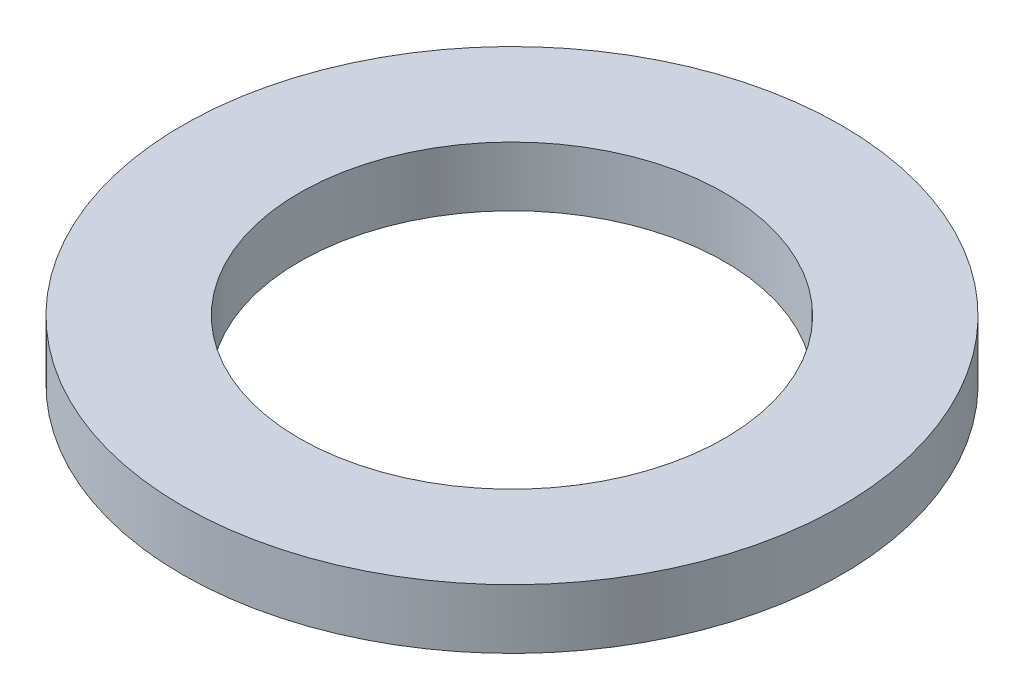
SolidWorks part; units mm, degrees
ref_plane "Front Plane" through (0, 0, 0) normal (0, 0, 1) x (1, 0, 0)
ref_plane "Top Plane" through (0, 0, 0) normal (0, 1, 0) x (1, 0, 0)
ref_plane "Right Plane" through (0, 0, 0) normal (1, 0, 0) x (0, 0, -1)
sketch "Sketch1" plane through (0, 0, 0) normal (0, 1, 0) x (1, 0, 0)
  circle A0 centre (0, 0) radius 77.5
  dimension "FLANGE_OD" = 155
extrude "Boss-Extrude1" add sketch "Sketch1" along normal blind 14
sketch "Sketch2" plane through (0, 0, 0) normal (0, 1, 0) x (1, 0, 0)
  circle A0 centre (0, 0) radius 50
  dimension "BORE_D" = 100
extrude "Cut-Extrude1" cut sketch "Sketch2" along normal through all
sketch "Sketch3" plane through (0, 14, 0) normal (0, 1, 0) x (1, 0, 0)
  circle A0 centre (0, 0) radius 30.8525 construction
  circle A1 centre (-30.8525, 0) radius 3.9763
  dimension "BOLT_D" = 7.9526
  dimension "BOLT_PCD" = 61.705
extrude "Cut-Extrude2" cut sketch "Sketch3" against normal blind 10.6411 rebuild error yes
pattern_circular "CirPattern1" count 3 over 360 rebuild error yes
